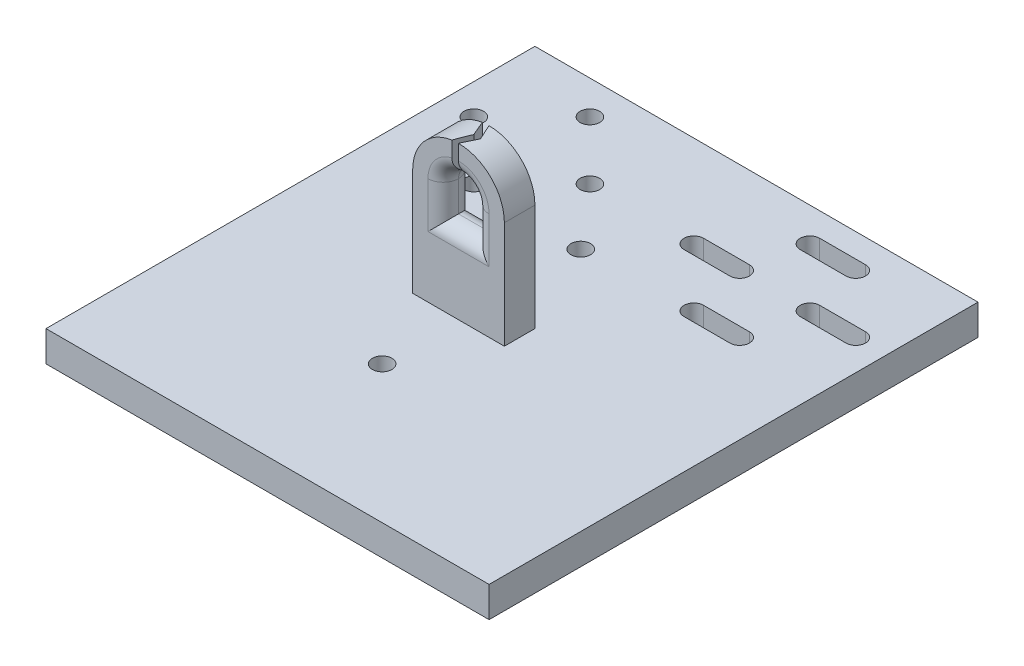
SolidWorks part; units mm, degrees
ref_plane "Front Plane" through (0, 0, 0) normal (0, 0, 1) x (1, 0, 0)
ref_plane "Top Plane" through (0, 0, 0) normal (0, 1, 0) x (1, 0, 0)
ref_plane "Right Plane" through (0, 0, 0) normal (1, 0, 0) x (0, 0, -1)
sketch "Sketch2" plane through (0, 0, 0) normal (0, 1, 0) x (1, 0, 0)
  line L1 (-32.5, 15) -> (32.5, 15)
  line L2 (-32.5, 15) -> (-32.5, -15)
  line L3 (-32.5, -15) -> (32.5, -15)
  line L4 (32.5, 15) -> (32.5, -15)
  line L5 (-32.5, 15) -> (32.5, -15) construction
  line L6 (-32.5, -15) -> (32.5, 15) construction
  point P0 (0, 0)
  dimension "D1" = 65
  dimension "D2" = 30
extrude "Boss-Extrude1" add sketch "Sketch2" along normal blind 5
sketch "Sketch3" plane through (0, 5, 0) normal (0, 1, 0) x (1, 0, 0)
  line L2 (0, 0) -> (0, 10.693) construction
  circle A0 centre (-27.5, 0) radius 1.6
  circle A8 centre (-18, 0) radius 16.7 construction
  circle A9 centre (-18, 9.5) radius 1.6
  circle A10 centre (-8.5, 0) radius 1.6
  circle A11 centre (-18, -9.5) radius 1.6
  circle A12 centre (18, -9.5) radius 1.6
  circle A13 centre (27.5, 0) radius 1.6
  circle A14 centre (18, 9.5) radius 1.6
  circle A15 centre (8.5, 0) radius 1.6
  dimension "D1" = 3.2
  dimension "D4" = 33.4
  dimension "D3" = 19
  dimension "D5" = 18
  dimension "D2" = 4
extrude "Cut-Extrude1" cut sketch "Sketch3" against normal through all
sketch "Sketch5" plane through (32.5, 0, 0) normal (1, 0, 0) x (0, 0, -1)
  line L4 (-15, 0) -> (15, 0)
  line L5 (15, 0) -> (15, 5)
  line L6 (15, 5) -> (-15, 5)
  line L7 (-15, 5) -> (-15, 0)
  line L8 (-15, 0) -> (15, 0)
  line L9 (15, 0) -> (15, 5)
  line L10 (15, 5) -> (-15, 5)
  line L11 (-15, 5) -> (-15, 0)
  dimension "D1" = 0
extrude "Boss-Extrude2" add sketch "Sketch5" along normal blind 7.5
sketch "Sketch4" plane through (0, 5, 0) normal (0, 1, 0) x (1, 0, 0)
  line L0 (8.5, 0) -> (16, 0) construction
  line L1 (8.5, 1.6) -> (16, 1.6)
  line L2 (8.5, -1.6) -> (16, -1.6)
  line L3 (27.5, 0) -> (35, 0) construction
  line L4 (27.5, 1.6) -> (35, 1.6)
  line L5 (27.5, -1.6) -> (35, -1.6)
  line L6 (18, -9.5) -> (25.5, -9.5) construction
  line L7 (18, -7.9) -> (25.5, -7.9)
  line L8 (18, -11.1) -> (25.5, -11.1)
  line L9 (18, 9.5) -> (25.5, 9.5) construction
  line L10 (18, 11.1) -> (25.5, 11.1)
  line L11 (18, 7.9) -> (25.5, 7.9)
  arc A0 (8.5, 1.6) -> (8.5, -1.6) centre (8.5, 0) ccw
  arc A1 (16, -1.6) -> (16, 1.6) centre (16, 0) ccw
  arc A2 (27.5, 1.6) -> (27.5, -1.6) centre (27.5, 0) ccw
  arc A3 (35, -1.6) -> (35, 1.6) centre (35, 0) ccw
  arc A4 (18, -7.9) -> (18, -11.1) centre (18, -9.5) ccw
  arc A5 (25.5, -11.1) -> (25.5, -7.9) centre (25.5, -9.5) ccw
  arc A6 (18, 11.1) -> (18, 7.9) centre (18, 9.5) ccw
  arc A7 (25.5, 7.9) -> (25.5, 11.1) centre (25.5, 9.5) ccw
  circle A8 centre (27.5, 0) radius 1.6 construction
  point P4 (12.25, 0)
  point P9 (31.25, 0)
  point P17 (21.75, -9.5)
  point P25 (21.75, 9.5)
  dimension "D1" = 7.5
extrude "Cut-Extrude2" cut sketch "Sketch4" against normal blind 10
sketch "Sketch7" plane through (0, 0, 15) normal (0, 0, 1) x (1, 0, 0)
  line L4 (-32.5, 0) -> (40, 0)
  line L5 (40, 0) -> (40, 5)
  line L6 (40, 5) -> (-32.5, 5)
  line L7 (-32.5, 5) -> (-32.5, 0)
  line L8 (-32.5, 0) -> (40, 0)
  line L9 (40, 0) -> (40, 5)
  line L10 (40, 5) -> (-32.5, 5)
  line L11 (-32.5, 5) -> (-32.5, 0)
  dimension "D1" = 0
extrude "Boss-Extrude3" add sketch "Sketch7" along normal blind 50
ref_plane "Plane1" through (0, 0, 25) normal (0, 0, 1) x (1, 0, 0)
sketch "Sketch10" plane through (0, 0, 25) normal (0, 0, 1) x (1, 0, 0)
  line L0 (40, 5) -> (-32.5, 5) construction
  line L1 (-7.5, 5) -> (7.5, 5)
  line L2 (-7.5, 5) -> (-7.5, 22.5)
  line L3 (-2.5, 17.5) -> (2.5, 17.5)
  line L4 (7.5, 5) -> (7.5, 22.5)
  line L16 (-7.5, 22.5) -> (-2.5, 22.5)
  line L17 (-2.5, 17.5) -> (-2.5, 22.5)
  line L20 (7.5, 22.5) -> (2.5, 22.5)
  line L21 (2.5, 17.5) -> (2.5, 22.5)
  point P1 (-9.7019, 14.7904)
  point P2 (7.5196, 10)
  point P6 (0, 5)
  point P14 (-10, 10)
  point P15 (10, 5)
  point P16 (10, 13.9831)
  point P17 (4.3578, 8.9378)
  point P18 (-9.7019, 10)
  point P19 (9.7019, 10)
  point P20 (9.7019, 10)
  point P21 (9.9077, 14.7904)
  dimension "D1" = 15
  dimension "D3" = 12.5
  dimension "D4" = 5
  dimension "D5" = 5
extrude "Boss-Extrude4" add sketch "Sketch10" along normal blind 5
sketch "Sketch11" plane through (0, 0, 30) normal (0, 0, 1) x (1, 0, 0)
  line L0 (-7.5, 22.5) -> (-2.5, 22.5)
  line L1 (2.5, 22.5) -> (7.5, 22.5)
  arc A0 (-7.5, 22.5) -> (7.5, 22.5) centre (0, 22.5) cw
  arc A1 (-2.5, 22.5) -> (2.5, 22.5) centre (0, 22.5) cw
  point P8 (0, 0)
  point P11 (0, 0)
extrude "Boss-Extrude5" add sketch "Sketch11" against normal blind 5
sketch "Sketch6" plane through (0, 0, 0) normal (0, -1, 0) x (1, 0, 0)
  line L0 (0, 42.5) -> (0, 10) construction
  line L1 (40, -15) -> (-32.5, -15) construction
  circle A0 centre (0, 42.5) radius 1.6
  circle A1 centre (0, 10) radius 1.6
  point P3 (5.8202, 0)
  point P6 (3.8909, 11.5901)
  dimension "D1" = 3.2
  dimension "D2" = 32.5
  dimension "D3" = 25
extrude "Cut-Extrude3" cut sketch "Sketch6" against normal blind 10
sketch "Sketch14" plane through (0, 17.5, 0) normal (0, 1, 0) x (1, 0, 0)
  line L0 (-1.0911, -25) -> (0, -27.5)
  line L1 (7.5, -25) -> (-7.5, -25) construction
  line L2 (0, -27.5) -> (-1.0911, -30)
  line L3 (-7.5, -30) -> (7.5, -30) construction
  line L4 (0, -25) -> (1.0911, -27.5)
  line L5 (1.0911, -27.5) -> (0, -30)
  line L6 (-1.0911, -25) -> (0, -25)
  line L7 (-1.0911, -30) -> (0, -30)
  line L8 (-7.5, -30) -> (7.5, -30)
  line L9 (7.5, -30) -> (7.5, -25)
  line L10 (7.5, -25) -> (-7.5, -25)
  line L11 (-7.5, -25) -> (-7.5, -30)
  line L12 (-7.5, -30) -> (7.5, -30) construction
  line L13 (7.5, -30) -> (7.5, -25) construction
  line L14 (7.5, -25) -> (-7.5, -25) construction
  line L15 (-7.5, -25) -> (-7.5, -30) construction
  point P12 (-7.5, -27.5)
  dimension "D2" = 1
  dimension "D1" = 0
extrude "Cut-Extrude4" cut sketch "Sketch14" along normal through all
fillet "Fillet1" radius 2.5 10 edges at (-2.5, 20, 25) (1.7678, 24.2678, 25) (1.7678, 24.2678, 30) (-2.1187, 23.8271, 30) (-2.1187, 23.8271, 25) (2.5, 20, 25) (0, 17.5, 25) (2.5, 20, 30) (0, 17.5, 30) (-2.5, 20, 30)
